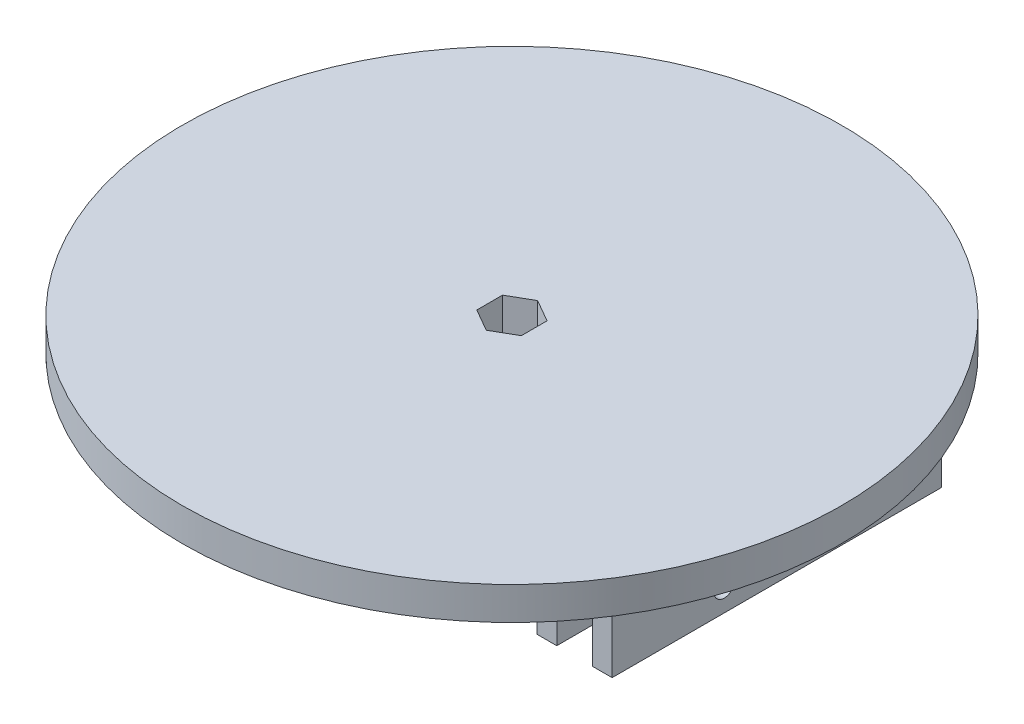
SolidWorks part; units mm, degrees
ref_plane "Front Plane" through (0, 0, 0) normal (0, 0, 1) x (1, 0, 0)
ref_plane "Top Plane" through (0, 0, 0) normal (0, 1, 0) x (1, 0, 0)
ref_plane "Right Plane" through (0, 0, 0) normal (1, 0, 0) x (0, 0, -1)
sketch "Sketch2" plane through (0, 0, 0) normal (0, 1, 0) x (1, 0, 0)
  circle A0 centre (0, 0) radius 9
extrude "Boss-Extrude1" add sketch "Sketch2" along normal blind 20
sketch "Sketch3" plane through (0, 20, 0) normal (0, 1, 0) x (1, 0, 0)
  line L0 (-3.3775, -1.95) -> (3.3775, 1.95) construction
  line L1 (0, -3.9) -> (0, 3.9) construction
  line L2 (3.3775, -1.95) -> (-3.3775, 1.95) construction
  line L15 (0, 3.9) -> (-3.3775, 1.95)
  line L16 (-3.3775, 1.95) -> (-3.3775, -1.95)
  line L17 (-3.3775, -1.95) -> (0, -3.9)
  line L18 (0, -3.9) -> (3.3775, -1.95)
  line L19 (3.3775, -1.95) -> (3.3775, 1.95)
  line L20 (3.3775, 1.95) -> (0, 3.9)
  circle A0 centre (0, 0) radius 3.9 construction
  point P4 (0, 0)
  point P5 (0, 0)
  point P6 (0, 0)
  point P9 (0, 0)
  point P10 (0, 0)
  point P11 (0, 0)
  point P14 (0, 0)
  point P15 (0, 0)
  point P17 (0, 0)
  point P20 (0, 0)
extrude "Cut-Extrude1" cut sketch "Sketch3" against normal blind 20
sketch "Sketch4" plane through (0, 20, 0) normal (0, 1, 0) x (1, 0, 0)
  circle A0 centre (0, 0) radius 50
  circle A1 centre (0, 0) radius 4.5
extrude "Boss-Extrude3" add sketch "Sketch4" against normal blind 5
ref_plane "Plane3" through (0, 0, 0) normal (0.5, 0, -0.866) x (-0.866, 0, -0.5)
sketch "Sketch11" plane through (0, 0, 0) normal (0.5, 0, -0.866) x (-0.866, 0, -0.5)
  line L2 (0, 0) -> (0, 5) construction
  circle A0 centre (0, 5) radius 1.55
extrude "Cut-Extrude2" cut sketch "Sketch11" against normal blind 9 and the other way blind 9
ref_plane "Plane4" through (0, 0, 0) normal (-0.5, 0, -0.866) x (-0.866, 0, 0.5)
sketch "Sketch15" plane through (0, 0, 0) normal (-0.5, 0, -0.866) x (-0.866, 0, 0.5)
  line L0 (0, 0) -> (0, 9) construction
  circle A0 centre (0, 9) radius 1.55
extrude "Cut-Extrude9" cut sketch "Sketch15" against normal blind 9 and the other way blind 9
sketch "Sketch16" plane through (0, 15, 0) normal (0, -1, 0) x (1, 0, 0)
  line L0 (0, 0) -> (31.8, 0) construction
  line L6 (0, 0) -> (-31.8, 0) construction
  line L12 (-31.8, -25) -> (-31.8, 25)
  line L13 (-31.8, 25) -> (-28.8, 25)
  line L14 (-28.8, 25) -> (-28.8, -25)
  line L15 (-28.8, -25) -> (-31.8, -25)
  line L16 (-31.8, 0) -> (-37.2, 0) construction
  line L17 (-37.2, -25) -> (-37.2, 25)
  line L18 (-37.2, 25) -> (-40.2, 25)
  line L19 (-40.2, 25) -> (-40.2, -25)
  line L20 (-40.2, -25) -> (-37.2, -25)
  line L21 (31.8, -25) -> (31.8, 25)
  line L22 (31.8, 25) -> (28.8, 25)
  line L23 (28.8, 25) -> (28.8, -25)
  line L24 (28.8, -25) -> (31.8, -25)
  line L25 (31.8, 0) -> (37.2, 0) construction
  line L26 (37.2, -25) -> (37.2, 25)
  line L27 (37.2, 25) -> (40.2, 25)
  line L28 (40.2, 25) -> (40.2, -25)
  line L29 (40.2, -25) -> (37.2, -25)
  point P7 (-31.8, 0)
  point P14 (-37.2, 0)
  point P19 (31.8, 0)
  point P25 (37.2, 0)
extrude "Boss-Extrude4" add sketch "Sketch16" along normal blind 10
sketch "Sketch17" plane through (-40.2, 0, 0) normal (-1, 0, 0) x (0, 0, 1)
  line L0 (-25, 5) -> (-25, 8.5) construction
  line L1 (-25, 5) -> (-25, 15) construction
  line L2 (-25, 8.5) -> (-8, 8.5) construction
  line L3 (-8, 8.5) -> (8, 8.5) construction
  line L4 (-16, 11.5) -> (16, 11.5) construction
  line L5 (-25, 15) -> (-25, 11.5) construction
  line L6 (-25, 11.5) -> (-16, 11.5) construction
  circle A0 centre (-16, 11.5) radius 1.55
  circle A1 centre (-8, 8.5) radius 1.55
  circle A3 centre (8, 8.5) radius 1.55
  circle A5 centre (16, 11.5) radius 1.55
extrude "Cut-Extrude10" cut sketch "Sketch17" against normal up to surface (11.4 mm away) up to face at (-28.8, 10, 0)
sketch "Sketch18" plane through (40.2, 0, 0) normal (1, 0, 0) x (0, 0, -1)
  line L0 (-25, 5) -> (-25, 8.5) construction
  line L1 (-25, 8.5) -> (-8, 8.5) construction
  line L2 (-8, 8.5) -> (8, 8.5) construction
  line L3 (8, 8.5) -> (-8, 8.5) construction
  line L4 (-25, 15) -> (-25, 11.5) construction
  line L5 (-25, 5) -> (-25, 15) construction
  line L6 (-25, 11.5) -> (-16, 11.5) construction
  line L7 (-16, 11.5) -> (16, 11.5) construction
  line L8 (16, 11.5) -> (-16, 11.5) construction
  circle A0 centre (-8, 8.5) radius 1.55
  circle A1 centre (8, 8.5) radius 1.55
  circle A2 centre (16, 11.5) radius 1.55
  circle A3 centre (-16, 11.5) radius 1.55
extrude "Cut-Extrude11" cut sketch "Sketch18" against normal up to surface (11.4 mm away) up to face at (28.8, 10, 0)
sketch "Sketch19" plane through (0, 0, 0) normal (-0.5, 0, -0.866) x (-0.866, 0, 0.5)
  circle A0 centre (0, 9) radius 3.5
extrude "Cut-Extrude14" cut sketch "Sketch19" against normal blind 3 from offset 9 contours A0
extrude "Cut-Extrude15" cut sketch "Sketch19<3>" along normal blind 3 from offset 9 offset against normal yes
sketch "Sketch19<3>" plane through (0, 0, 0) normal (-0.5, 0, -0.866) x (-0.866, 0, 0.5) same geometry as "Sketch19"
sketch "Sketch20" plane through (0, 0, 0) normal (0.5, 0, -0.866) x (-0.866, 0, -0.5)
  circle A0 centre (0, 5) radius 3.5
extrude "Cut-Extrude16" cut sketch "Sketch20" against normal blind 3 from offset 9
extrude "Cut-Extrude17" cut sketch "Sketch20<2>" along normal blind 3 from offset 9 offset against normal yes
sketch "Sketch20<2>" plane through (0, 0, 0) normal (0.5, 0, -0.866) x (-0.866, 0, -0.5) same geometry as "Sketch20"
